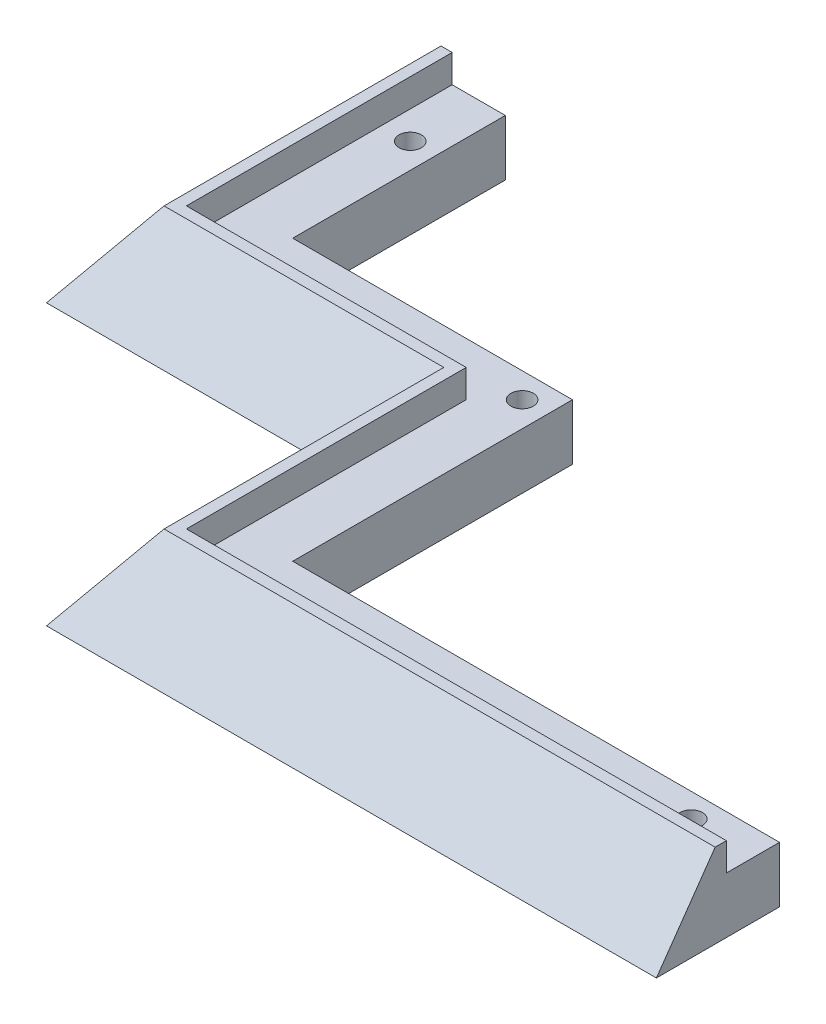
SolidWorks part; units mm, degrees
ref_plane "Plan de face" through (0, 0, 0) normal (0, 0, 1) x (1, 0, 0)
ref_plane "Plan de dessus" through (0, 0, 0) normal (0, 1, 0) x (1, 0, 0)
ref_plane "Plan de droite" through (0, 0, 0) normal (1, 0, 0) x (0, 0, -1)
sketch "Esquisse1" plane through (0, 0, 0) normal (0, 1, 0) x (1, 0, 0)
  line L0 (-41.3523, -18.6477) -> (8.6477, -18.6477)
  line L1 (68.6477, -68.6477) -> (8.6477, -68.6477)
  line L3 (-19.3523, 41.3523) -> (-41.3523, 41.3523)
  line L4 (-41.3523, -18.6477) -> (-41.3523, 41.3523)
  line L5 (68.6477, -68.6477) -> (-41.3523, 41.3523) construction
  line L6 (55, 80) -> (-55, -80) construction
  line L7 (8.6477, -18.6477) -> (8.6477, -68.6477)
  line L8 (-19.3523, 41.3523) -> (-19.3523, 3.3523)
  line L9 (-19.3523, 3.3523) -> (30.6477, 3.3523)
  line L10 (30.6477, 3.3523) -> (30.6477, -46.6477)
  line L11 (30.6477, -46.6477) -> (68.6477, -46.6477)
  line L12 (68.6477, -68.6477) -> (117.6477, -68.6477)
  line L13 (117.6477, -68.6477) -> (117.6477, -46.6477)
  line L14 (117.6477, -46.6477) -> (68.6477, -46.6477)
  point P0 (0, 0)
  dimension "D1" = 110
  dimension "D2" = 110
  dimension "D3" = 50
  dimension "D4" = 22
  dimension "D5" = 22
  dimension "D6" = 22
  dimension "D7" = 22
  dimension "D8" = 49
extrude "Boss.-Extru.1" add sketch "Esquisse1" along normal blind 15
chamfer "Chanfrein1" distance 15 angle 35 4 edges at (63.1477, 15, 68.6477) (8.6477, 15, 43.6477) (-16.3523, 15, 18.6477) (-41.3523, 15, -11.3523) first distance on face at (63.1477, 7.5, 68.6477) first distance on face at (8.6477, 7.5, 43.6477) first distance on face at (-16.3523, 7.5, 18.6477) first distance on face at (-41.3523, 7.5, -11.3523)
sketch "Esquisse4" plane through (0, 0, 0) normal (0, -1, 0) x (1, 0, 0)
  line L0 (-36.3523, -36.3523) -> (-36.3523, 13.6477) construction
  line L1 (-19.3523, -41.3523) -> (-41.3523, -41.3523) construction
  line L2 (-41.3523, 18.6477) -> (8.6477, 18.6477) construction
  line L3 (-36.3523, 13.6477) -> (13.6477, 13.6477) construction
  line L4 (-41.3523, -41.3523) -> (-41.3523, 18.6477) construction
  line L5 (117.6477, 68.6477) -> (117.6477, 46.6477) construction
  line L6 (63.6477, 63.6477) -> (13.6477, 63.6477) construction
  line L8 (8.6477, 18.6477) -> (8.6477, 68.6477) construction
  line L9 (13.6477, 63.6477) -> (13.6477, 13.6477) construction
  line L10 (8.6477, 68.6477) -> (117.6477, 68.6477) construction
  line L12 (-19.3523, -36.3523) -> (-36.3523, -36.3523) construction
  line L13 (-19.3523, -3.3523) -> (-19.3523, -41.3523) construction
  line L14 (63.6477, 46.6477) -> (63.6477, 63.6477) construction
  line L15 (117.6477, 46.6477) -> (30.6477, 46.6477) construction
  circle A0 centre (38.6477, 63.6477) radius 2
  circle A1 centre (13.6477, 38.6477) radius 2
  circle A2 centre (-11.3523, 13.6477) radius 2
  dimension "D7" = 4
  dimension "D1" = 5
  dimension "D2" = 5
  dimension "D3" = 5
  dimension "D4" = 5
  dimension "D5" = 54
  dimension "D6" = 5
extrude "Enlèv. mat.-Extru.3" cut sketch "Esquisse4" against normal blind 4
sketch "Esquisse5" plane through (0, 15, 0) normal (0, 1, 0) x (1, 0, 0)
  line L0 (-28.8492, 41.3523) -> (-19.3523, 41.3523)
  line L1 (-19.3523, 41.3523) -> (-30.8492, 41.3523) construction
  line L2 (-19.3523, 41.3523) -> (-19.3523, 3.3523)
  line L3 (-19.3523, 3.3523) -> (30.6477, 3.3523)
  line L4 (30.6477, 3.3523) -> (30.6477, -46.6477)
  line L9 (21.1508, -56.1404) -> (21.1508, -6.1445)
  line L10 (21.1508, -6.1445) -> (-28.8492, -6.1445)
  line L11 (-28.8492, -6.1445) -> (-28.8492, 41.3523)
  line L12 (-30.8492, 41.3523) -> (-30.8492, -8.1445) construction
  line L14 (-30.8492, -8.1445) -> (19.1508, -8.1445) construction
  line L15 (19.1508, -8.1445) -> (19.1508, -58.1445) construction
  line L16 (21.1508, -56.1404) -> (117.6477, -56.1404)
  line L17 (117.6477, -58.1445) -> (117.6477, -46.6477) construction
  line L18 (117.6477, -56.1404) -> (117.6477, -46.6477)
  line L19 (117.6477, -46.6477) -> (30.6477, -46.6477)
  line L20 (19.1508, -58.1445) -> (117.6477, -58.1445) construction
  dimension "D1" = 2
  dimension "D2" = 2.0042
  dimension "D3" = 2
  dimension "D4" = 2
extrude "Enlèv. mat.-Extru.5" cut sketch "Esquisse5" against normal blind 5
sketch "Esquisse6" plane through (0, 10, 0) normal (0, 1, 0) x (1, 0, 0)
  line L0 (-23.8492, 41.3523) -> (-23.8492, -1.1445) construction
  line L1 (-19.3523, 41.3523) -> (-28.8492, 41.3523) construction
  line L2 (-23.8492, -1.1445) -> (26.1508, -1.1445) construction
  line L3 (26.1508, -1.1445) -> (26.1508, -51.1404) construction
  line L4 (26.1508, -51.1404) -> (117.6477, -51.1404) construction
  line L6 (-28.8492, 41.3523) -> (-28.8492, -6.1445) construction
  line L7 (-28.8492, -6.1445) -> (21.1508, -6.1445) construction
  line L8 (21.1508, -6.1445) -> (21.1508, -56.1404) construction
  line L11 (117.6477, -46.6477) -> (30.6477, -46.6477) construction
  line L12 (21.1508, -56.1404) -> (117.6477, -56.1404) construction
  circle A0 centre (-23.8492, 28.8555) radius 2
  circle A1 centre (26.1508, -1.1445) radius 2
  circle A2 centre (106.1505, -50.9186) radius 2
  dimension "D5" = 4
  dimension "D1" = 5
  dimension "D2" = 5
  dimension "D3" = 5
  dimension "D4" = 5
  dimension "D6" = 30
  dimension "D7" = 80
extrude "Enlèv. mat.-Extru.6" cut sketch "Esquisse6" against normal blind 5
